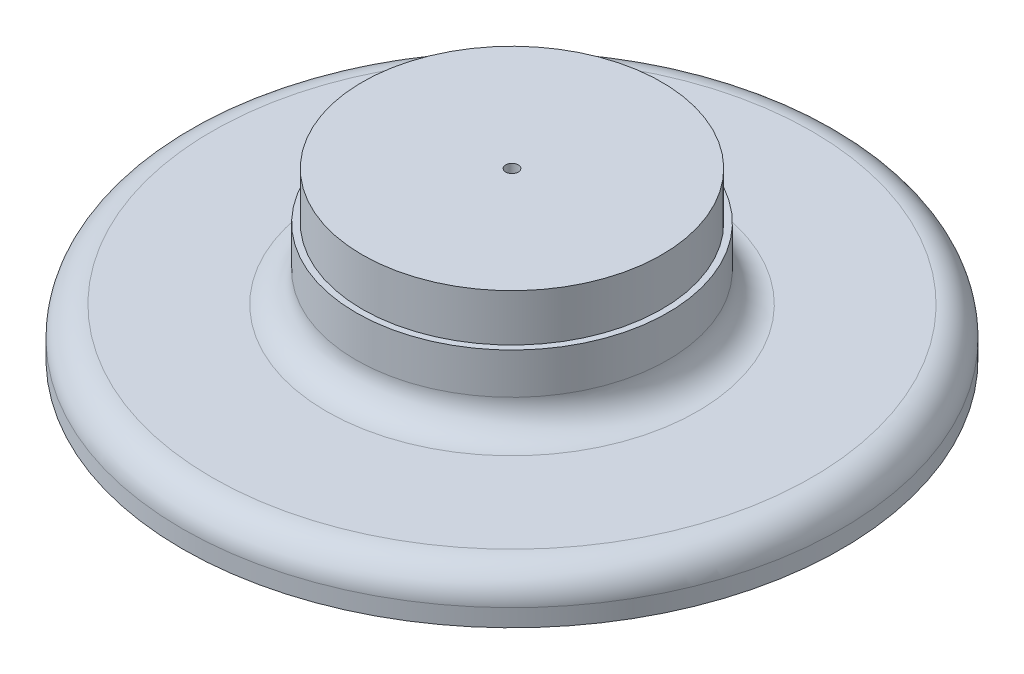
SolidWorks part; units mm, degrees
ref_plane "Front Plane" through (0, 0, 0) normal (0, 0, 1) x (1, 0, 0)
ref_plane "Top Plane" through (0, 0, 0) normal (0, 1, 0) x (1, 0, 0)
ref_plane "Right Plane" through (0, 0, 0) normal (1, 0, 0) x (0, 0, -1)
sketch "Sketch1" plane through (0, 0, 0) normal (0, 1, 0) x (1, 0, 0)
  circle A0 centre (0, 0) radius 80.772
  circle A1 centre (0, 0) radius 84.074
  circle A2 centre (0, 0) radius 177.8
extrude "Boss-Extrude1" add sketch "Sketch1" along normal blind 88.9 contours A0 region at (0, 0, 0)
extrude "Boss-Extrude2" add sketch "Sketch1<3>" along normal blind 63.5 contours A1 A0 region at (-81.696, 0, 0)
sketch "Sketch1<3>" plane through (0, 0, 0) normal (0, 1, 0) x (1, 0, 0) same geometry as "Sketch1"
extrude "Boss-Extrude3" add sketch "Sketch1<4>" along normal blind 25.4 contours A2 A1 region at (-172.7711, 0, 0)
sketch "Sketch1<4>" plane through (0, 0, 0) normal (0, 1, 0) x (1, 0, 0) same geometry as "Sketch1"
hole_wizard "CSK for 1/4 Flat Head Machine Screw (100)1" positions "Sketch2" profile "Sketch3" countersink size "1/4" standard "ANSI Inch" end condition through all
sketch "Sketch2" plane through (0, 0, 0) normal (0, -1, 0) x (-1, 0, 0)
  point P0 (0, 0)
sketch "Sketch3" plane through (0, 0, 0) normal (1, 0, 0) x (0, 0, -1)
  line L0 (0, 0) -> (0, 88.9)
  line L1 (0, 88.9) -> (3.3782, 88.9)
  line L2 (3.3782, 88.9) -> (3.3782, 2.5682)
  line L3 (3.3782, 2.5682) -> (6.4389, 0)
  line L5 (6.4389, 0) -> (0, 0)
  line L6 (-3.3782, 2.5682) -> (-6.4389, 0) construction
  line L11 (0, -6.35) -> (0, 107.95) construction
  dimension "Thru Hole Dia." = 6.7564
  dimension "Thru Hole Depth" = 88.9
  dimension "Near C'Sink Dia." = 12.8778
  dimension "Near C'Sink Angle" = 100
fillet "Fillet1" radius 16.002 1 edges at (0, 25.4, 84.074)
fillet "Fillet2" radius 16.002 1 edges at (0, 25.4, 177.8)
